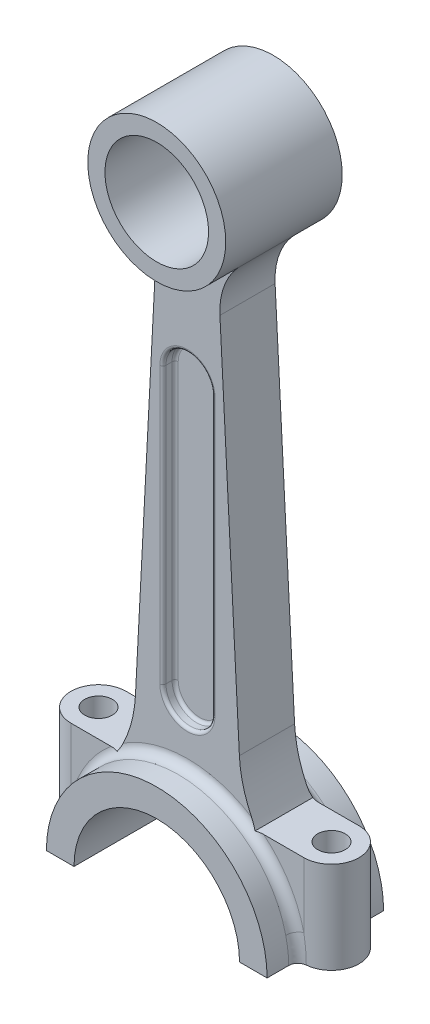
SolidWorks part; units mm, degrees
ref_plane "Front Plane" through (0, 0, 0) normal (0, 0, 1) x (1, 0, 0)
ref_plane "Top Plane" through (0, 0, 0) normal (0, 1, 0) x (1, 0, 0)
ref_plane "Right Plane" through (0, 0, 0) normal (1, 0, 0) x (0, 0, -1)
sketch "Sketch1" plane through (0, 0, 0) normal (0, 0, 1) x (1, 0, 0)
  line L0 (0, 0) -> (0, -174.2) construction
  line L1 (-10, -20.1556) -> (-17.8497, -169.9368)
  line L2 (10, -20.1556) -> (17.8497, -169.9368)
  line L3 (36, -201.2) -> (27, -201.2)
  line L4 (-27, -201.2) -> (-36, -201.2)
  circle A0 centre (0, 0) radius 22.5
  circle A1 centre (0, 0) radius 16.9
  arc A2 (27, -201.2) -> (-27, -201.2) centre (0, -201.2) ccw
  arc A3 (36, -201.2) -> (-36, -201.2) centre (0, -201.2) ccw
  dimension "D1" = 45
  dimension "D2" = 33.8
  dimension "D3" = 54
  dimension "D4" = 72
  dimension "D5" = 201.2
  dimension "D6" = 6
  dimension "D7" = 20
extrude "Boss-Extrude1" add sketch "Sketch1" along normal mid plane 38 contours A1 A0 | A3 A2 | L0 A3 L4 A2 region at (-4.9903, -21.2865, 0) region at (20.1899, -181.0101, 0) region at (-20.1899, -181.0101, 0)
extrude "Boss-Extrude2" add sketch "Sketch1<3>" along normal mid plane 18 contours A0 L0 A3 L2 | L0 A0 L1 A3 region at (7.1843, -100.8455, 0) region at (-7.1843, -100.8455, 0)
sketch "Sketch1<3>" plane through (0, 0, 0) normal (0, 0, 1) x (1, 0, 0) same geometry as "Sketch1"
sketch "Sketch2" plane through (0, 0, 9) normal (0, 0, 1) x (1, 0, 0)
  line L0 (0, 0) -> (0, -201.2) construction
  line L1 (0, -145.6) -> (0, -55.6) construction
  line L2 (-8, -145.6) -> (-8, -55.6)
  line L3 (8, -145.6) -> (8, -55.6)
  arc A0 (-8, -145.6) -> (8, -145.6) centre (0, -145.6) ccw
  arc A1 (8, -55.6) -> (-8, -55.6) centre (0, -55.6) ccw
  point P6 (0, -100.6)
  dimension "D2" = 8
  dimension "D1" = 90
extrude "Cut-Extrude1" cut sketch "Sketch2" against normal blind 4
mirror "Mirror1" about plane through (0, 0, 0) normal (0, 0, 1) of "Cut-Extrude1"
fillet "Fillet1" radius 1 16 edges at (0, -47.6, -9) (8, -100.6, -9) (0, -153.6, -9) (0, -47.6, 9) (8, -100.6, 9) (0, -153.6, 9) (0, -47.6, 5) (8, -100.6, 5) (0, -153.6, 5) (8, -100.6, -5) (0, -47.6, -5) (-8, -100.6, -5) (0, -153.6, -5) (-8, -100.6, -9) (-8, -100.6, 9) (-8, -100.6, 5)
fillet "Fillet2" radius 40 2 edges at (17.8497, -169.9368, 0) (-17.8497, -169.9368, 0)
fillet "Fillet3" radius 22.5 2 edges at (-10, -20.1556, 0) (10, -20.1556, 0)
ref_plane "Plane1" through (0, -171.2, 0) normal (0, -1, 0) x (-1, 0, 0)
sketch "Sketch5" plane through (0, -171.2, 0) normal (0, -1, 0) x (-1, 0, 0)
  line L0 (-38, 0) -> (38, 0) construction
  line L1 (-38, 9) -> (38, 9)
  line L2 (-38, -9) -> (38, -9)
  arc A0 (-38, 9) -> (-38, -9) centre (-38, 0) ccw
  arc A1 (38, -9) -> (38, 9) centre (38, 0) ccw
  point P2 (0, 0)
  dimension "D2" = 9
  dimension "D1" = 76
extrude "Boss-Extrude4" add sketch "Sketch5" along normal up to surface (30 mm away) up to face at (-31.5, -201.2, 0)
sketch "Sketch7" plane through (0, 0, 0) normal (0, 0, 1) x (1, 0, 0)
  line L1 (-27, -201.2) -> (27, -201.2)
  line L2 (-27, -201.2) -> (27, -201.2)
  arc A1 (27, -201.2) -> (-27, -201.2) centre (0, -201.2) ccw
  arc A2 (27, -201.2) -> (-27, -201.2) centre (0, -201.2) ccw
  dimension "D1" = 0
extrude "Cut-Extrude2" cut sketch "Sketch7" against normal through all both and the other way through all
sketch "Sketch8" plane through (0, -171.2, 0) normal (0, 1, 0) x (1, 0, 0)
  circle A0 centre (-38, 0) radius 4.5
  circle A1 centre (38, 0) radius 4.5
  dimension "D1" = 9
  dimension "D2" = 9
extrude "Cut-Extrude3" cut sketch "Sketch8" against normal through all
fillet "Fillet4" radius 3 2 edges at (0, -165.2, -9) (0, -165.2, 9)
